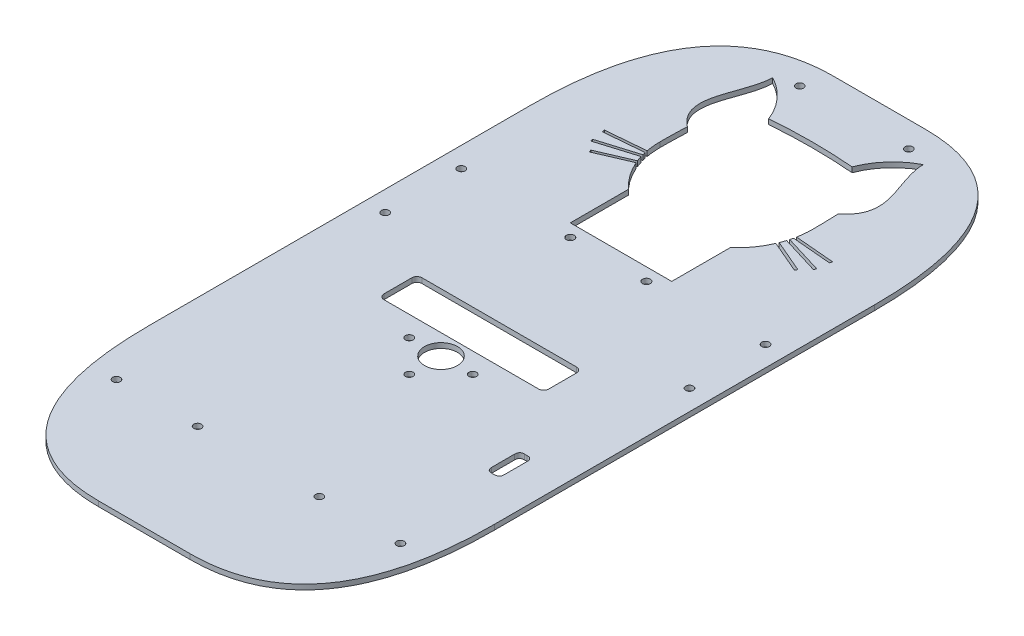
SolidWorks part; units mm, degrees
ref_plane "Спереди" through (0, 0, 0) normal (0, 0, 1) x (1, 0, 0)
ref_plane "Сверху" through (0, 0, 0) normal (0, 1, 0) x (1, 0, 0)
ref_plane "Справа" through (0, 0, 0) normal (1, 0, 0) x (0, 0, -1)
sketch "Эскиз1" plane through (0, 0, 0) normal (0, 1, 0) x (1, 0, 0)
  line L0 (0, 160) -> (0, -130) construction
  line L1 (-68, 160) -> (68, 160)
  line L2 (-68, 160) -> (-68, -130)
  line L3 (-68, -130) -> (68, -130)
  line L4 (68, 160) -> (68, -130)
  line L5 (-68, 0) -> (68, 0) construction
  dimension "D1" = 136
  dimension "D2" = 160
  dimension "D3" = 130
extrude "тело" add sketch "Эскиз1" along normal blind 2
sketch "Эскиз12" plane through (0, 2, 0) normal (0, 1, 0) x (1, 0, 0)
  line L0 (0, 160) -> (0, -130) construction
  line L1 (68, 160) -> (-68, 160) construction
  line L2 (-68, -130) -> (68, -130) construction
  line L3 (60, 55) -> (60, 25) construction
  line L4 (60, 40) -> (-60, 40) construction
  line L5 (-60, 55) -> (-60, 25) construction
  circle A0 centre (60, 55) radius 1.5
  circle A1 centre (-60, 55) radius 1.5
  circle A2 centre (-60, 25) radius 1.5
  circle A3 centre (60, 25) radius 1.5
  point P12 (-60, 40)
  point P17 (0, 40)
  dimension "D2" = 3
  dimension "D1" = 30
  dimension "D3" = 60
  dimension "D4" = 40
extrude "крепление подвески" cut sketch "Эскиз12" against normal through all
sketch "Эскиз8" plane through (0, 2, 0) normal (0, 1, 0) x (1, 0, 0)
  line L0 (-20, -130) -> (20, -130) construction
  line L1 (0, -130) -> (0, 160) construction
  line L2 (-68, -130) -> (68, -130) construction
  line L3 (68, 160) -> (-68, 160) construction
  circle A0 centre (-20, -130) radius 1.5
  circle A1 centre (20, -130) radius 1.5
  point P10 (0, -130)
  dimension "D1" = 3
  dimension "D2" = 40
  dimension "D3" = 130
extrude "крепление камеры" [suppressed] cut sketch "Эскиз8" against normal through all and the other way through all
sketch "Эскиз13" plane through (0, 2, 0) normal (0, 1, 0) x (1, 0, 0)
  line L0 (0, 160) -> (0, -130) construction
  line L1 (68, 160) -> (-68, 160) construction
  line L2 (-68, -130) -> (68, -130) construction
  line L3 (-57, 125) -> (57, 125) construction
  line L4 (-68, 15) -> (68, 15) construction
  line L5 (-57, -10) -> (57, -10) construction
  line L6 (-68, 160) -> (-68, -130) construction
  line L7 (-57, -85) -> (57, -85) construction
  line L8 (68, -130) -> (68, 160) construction
  line L9 (-25, 125) -> (-57, 125) construction
  line L10 (25, 125) -> (57, 125) construction
  line L11 (-57, -10) -> (-25, -10) construction
  line L12 (25, -10) -> (57, -10) construction
  line L13 (-57, -85) -> (-25, -85) construction
  line L14 (25, -85) -> (57, -85) construction
  circle A0 centre (-57, 125) radius 1.5
  circle A1 centre (57, 125) radius 1.5
  circle A2 centre (57, -10) radius 1.5
  circle A3 centre (-57, -10) radius 1.5
  circle A4 centre (-57, -85) radius 1.5
  circle A5 centre (57, -85) radius 1.5
  circle A6 centre (-25, 125) radius 1.5
  circle A7 centre (25, 125) radius 1.5
  circle A8 centre (25, -10) radius 1.5
  circle A9 centre (-25, -10) radius 1.5
  circle A10 centre (-25, -85) radius 1.5
  circle A11 centre (25, -85) radius 1.5
  point P18 (0, 125)
  point P19 (0, -10)
  point P20 (0, -85)
  point P27 (0, 15)
  dimension "D1" = 3
  dimension "D2" = 110
  dimension "D3" = 25
  dimension "D4" = 100
  dimension "D5" = 114
  dimension "D6" = 32
  dimension "D7" = 32
  dimension "D8" = 32
  dimension "D9" = 32
  dimension "D10" = 32
  dimension "D11" = 32
extrude "крепления уголков" [suppressed] cut sketch "Эскиз13" against normal through all
sketch "Эскиз9" plane through (0, 2, 0) normal (0, 1, 0) x (1, 0, 0)
  line L0 (0, -50) -> (0, 50) construction
  line L2 (-68, -130) -> (68, -130) construction
  circle A0 centre (0, -13) radius 6.5
  circle A1 centre (0, -13) radius 12.5 construction
  circle A2 centre (0, -0.5) radius 1.5
  circle A3 centre (12.5, -13) radius 1.5
  circle A4 centre (-12.5, -13) radius 1.5
  circle A5 centre (0, -25.5) radius 1.5
  point P4 (0, -17.1656)
  dimension "D2" = 13
  dimension "D3" = 25
  dimension "D4" = 3
  dimension "D1" = 117
extrude "ось вращения качалки" cut sketch "Эскиз9" against normal through all
sketch "Эскиз5" plane through (0, 2, 0) normal (0, 1, 0) x (1, 0, 0)
  line L0 (-50, -65) -> (50, -25) construction
  line L1 (-50, -25) -> (50, -25) construction
  line L2 (-50, -25) -> (-50, -65) construction
  line L3 (-50, -65) -> (50, -65) construction
  line L4 (50, -25) -> (50, -65) construction
  line L5 (-50, -25) -> (50, -65) construction
  line L6 (-68, -130) -> (68, -130) construction
  circle A0 centre (-50, -25) radius 1.5
  circle A1 centre (50, -25) radius 1.5
  circle A2 centre (50, -65) radius 1.5
  circle A3 centre (-50, -65) radius 1.5
  point P12 (0, -45)
  dimension "D1" = 3
  dimension "D2" = 100
  dimension "D3" = 40
  dimension "D4" = 65
extrude "крепление raspberry" [suppressed] cut sketch "Эскиз5" against normal through all
sketch "Эскиз11" plane through (0, 2, 0) normal (0, 1, 0) x (1, 0, 0)
  line L0 (-32.5, 2.5) -> (32.5, 2.5) construction
  line L1 (-32.5, 10) -> (32.5, 10)
  line L2 (-32.5, 10) -> (-32.5, -5)
  line L3 (-32.5, -5) -> (32.5, -5)
  line L4 (32.5, 10) -> (32.5, -5)
  point P11 (0, 10)
  dimension "D1" = 65
  dimension "D2" = 15
extrude "отверстие под провода на нижний этаж" cut sketch "Эскиз11" against normal through all
fillet "Скругление3" radius 2 4 edges at (-32.5, 1, 5) (32.5, 1, 5) (32.5, 1, -10) (-32.5, 1, -10)
sketch "Эскиз14" [suppressed] plane through (0, 2, 0) normal (0, 1, 0) x (1, 0, 0)
  line L0 (0, 160) -> (0, -130) construction
  line L1 (68, 160) -> (-68, 160) construction
  line L2 (-68, -130) -> (68, -130) construction
  line L3 (-47.5, -125) -> (47.5, -125) construction
  line L4 (47.5, -115) -> (47.5, -135) construction
  line L5 (-12.5, -95) -> (12.5, -95) construction
  line L6 (-47.5, -115) -> (-47.5, -135) construction
  circle A0 centre (-47.5, -115) radius 1.5
  circle A1 centre (-47.5, -135) radius 1.5
  circle A2 centre (47.5, -115) radius 1.5
  circle A3 centre (47.5, -135) radius 1.5
  point P8 (0, -125)
  point P14 (-47.5, -125)
  point P15 (47.5, -125)
  dimension "D1" = 3
  dimension "D2" = 20
  dimension "D3" = 30
  dimension "D4" = 95
extrude "крепление стопоров" [suppressed] cut sketch "Эскиз14" against normal through all
sketch "Эскиз15" plane through (0, 2, 0) normal (0, 1, 0) x (1, 0, 0)
  line L0 (-21.5, 150) -> (21.5, 150) construction
  line L1 (68, 160) -> (-68, 160) construction
  circle A0 centre (21.5, 150) radius 1.5
  circle A1 centre (-21.5, 150) radius 1.5
  point P6 (0, 150)
  dimension "D1" = 3
  dimension "D2" = 10
  dimension "D3" = 43
extrude "Крепление фронтальной камеры" cut sketch "Эскиз15" against normal up to next
sketch "Эскиз16" plane through (0, 2, 0) normal (0, 1, 0) x (1, 0, 0)
  line L0 (-56, -85) -> (-24, -85) construction
  line L1 (-68, -130) -> (68, -130) construction
  line L2 (-68, 160) -> (-68, -130) construction
  line L3 (0, -130) -> (0, 160) construction
  line L4 (68, 160) -> (-68, 160) construction
  circle A0 centre (-56, -85) radius 1.5
  circle A1 centre (-24, -85) radius 1.5
  circle A2 centre (24, -85) radius 1.5
  circle A3 centre (56, -85) radius 1.5
  dimension "D1" = 32
  dimension "D4" = 3
  dimension "D2" = 45
  dimension "D3" = 12
extrude "Крепление силовых уголков со стороны буллета" cut sketch "Эскиз16" against normal up to next
sketch "Эскиз17" plane through (0, 2, 0) normal (0, 1, 0) x (1, 0, 0)
  line L1 (48, -30) -> (53, -30)
  line L2 (48, -30) -> (48, -43)
  line L3 (48, -43) -> (53, -43)
  line L4 (53, -30) -> (53, -43)
  dimension "D2" = 13
  dimension "D3" = 5
extrude "Отверстие по дпитание сервоприводов и шилда" cut sketch "Эскиз17" against normal up to next
sketch "Эскиз18" plane through (0, 2, 0) normal (0, 1, 0) x (1, 0, 0)
  line L0 (0, 0) -> (0, 160) construction
  line L1 (68, 160) -> (-68, 160) construction
  line L2 (-20, 58) -> (20, 58)
  line L3 (20, 58) -> (20, 81)
  line L5 (-20, 81) -> (-20, 58)
  line L6 (10, 58) -> (10, 43)
  line L7 (10, 43) -> (-10, 43)
  line L8 (-10, 43) -> (-10, 58)
  line L9 (28.2843, 93.3607) -> (-28.2843, 93.3607)
  line L11 (-29.2696, 96.7813) -> (-44.8695, 95.4286)
  line L12 (15, 53) -> (-15, 53) construction
  line L13 (-28.6963, 94.613) -> (-43.9353, 89.9676)
  line L16 (-27.5654, 91.5223) -> (-40.4203, 86.0016)
  line L17 (-29.474, 97.7673) -> (-44.9559, 96.4249)
  line L18 (-28.972, 95.5744) -> (-44.2269, 90.9242)
  line L19 (-27.9447, 92.4477) -> (-40.8149, 86.9204)
  line L20 (-44.9559, 96.4249) -> (-44.8695, 95.4286)
  line L21 (-44.2269, 90.9242) -> (-43.9353, 89.9676)
  line L22 (-40.8149, 86.9204) -> (-40.4203, 86.0016)
  line L23 (-29.356, 97.7776) -> (-44.9559, 96.4249) construction
  line L24 (-28.6804, 94.6179) -> (-43.9353, 89.9676) construction
  line L25 (-27.5501, 91.5289) -> (-40.4203, 86.0016) construction
  line L26 (40.8149, 86.9204) -> (40.4203, 86.0016)
  line L27 (44.2269, 90.9242) -> (43.9353, 89.9676)
  line L28 (44.9559, 96.4249) -> (44.8695, 95.4286)
  line L29 (27.9447, 92.4477) -> (40.8149, 86.9204)
  line L30 (28.972, 95.5744) -> (44.2269, 90.9242)
  line L31 (29.474, 97.7673) -> (44.9559, 96.4249)
  line L32 (27.5654, 91.5223) -> (40.4203, 86.0016)
  line L33 (28.6963, 94.613) -> (43.9353, 89.9676)
  line L34 (29.2696, 96.7813) -> (44.8695, 95.4286)
  arc A0 (20, 81) -> (-20, 81) centre (0, 103.3607) ccw construction
  circle A1 centre (15, 53) radius 1.55
  circle A2 centre (-15, 53) radius 1.55
  arc A4 (-30, 103.3607) -> (-28.2843, 131.3607) centre (199.3322, 103.3607) cw
  arc A5 (-28.2843, 131.3607) -> (28.2843, 131.3607) centre (0, -67.6393) cw
  arc A6 (28.2843, 131.3607) -> (30, 103.3607) centre (-199.3322, 103.3607) cw
  arc A7 (-20, 81) -> (-27.5654, 91.5223) centre (0, 103.3607) cw
  arc A8 (20, 81) -> (27.5654, 91.5223) centre (0, 103.3607) ccw
  arc A9 (29.474, 97.7673) -> (30, 103.3607) centre (0, 103.3607) ccw
  arc A10 (-29.7135, 147.5209) -> (-16.4423, 132.687) centre (-42.569, 122.6661) cw
  arc A11 (29.7135, 147.5209) -> (16.4423, 132.687) centre (42.569, 122.6661) ccw
  arc A12 (28.972, 95.5744) -> (29.2696, 96.7813) centre (0, 103.3607) ccw
  arc A13 (27.9447, 92.4477) -> (28.6963, 94.613) centre (0, 103.3607) ccw
  arc A14 (-27.9447, 92.4477) -> (-28.6963, 94.613) centre (0, 103.3607) cw
  arc A15 (-28.972, 95.5744) -> (-29.2696, 96.7813) centre (0, 103.3607) cw
  arc A16 (-29.474, 97.7673) -> (-30, 103.3607) centre (0, 103.3607) cw
  spline S0 degree 3 poles (-29.7571, 113.9123) (-42.1018, 123.5014) (-29.7562, 136.265) (-29.7135, 147.5209) knots 0 0 0 0 1 1 1 1
  spline S1 degree 3 poles (29.7571, 113.9123) (42.1018, 123.5014) (29.7562, 136.265) (29.7135, 147.5209) knots 0 0 0 0 1 1 1 1
  point P9 (0, 43)
  point P15 (0, 58)
  point P25 (0, 53)
  dimension "D6" = 60
  dimension "D8" = 3.1
  dimension "D1" = 40
  dimension "D2" = 20
  dimension "D3" = 15
  dimension "D4" = 23
  dimension "D5" = 10
  dimension "D9" = 5
  dimension "D10" = 30
  dimension "D11" = 38
  dimension "D12" = 56.5685
  dimension "D13" = 1
  dimension "D14" = 1
  dimension "D15" = 1
fillet "Скругление4" radius 50 2 edges at (68, 1, 130) (-68, 1, -160) second distance 70 conic rho 0.5 first distance on face at (0, 1, 130) first distance on face at (0, 1, -160)
fillet "Скругление5" radius 70 2 edges at (-68, 1, 130) (68, 1, -160) second distance 50 conic rho 0.5 first distance on face at (-68, 1.25, -35) first distance on face at (68, 1.25, 5)
fillet "Скругление6" radius 2 4 edges at (48, 1, 43) (53, 1, 43) (48, 1, 30) (53, 1, 30) conic rho 0.5
sketch "Эскиз19" plane through (0, 2, 0) normal (0, 1, 0) x (1, 0, 0)
  line L1 (-95.3857, 162.9355) -> (76.7354, 162.9355)
  line L2 (-95.3857, 162.9355) -> (-95.3857, 60)
  line L3 (-95.3857, 60) -> (76.7354, 60)
  line L4 (76.7354, 162.9355) -> (76.7354, 60)
  circle A0 centre (-60, 55) radius 1.5 construction
  dimension "D1" = 5
extrude "Вырез-Вытянуть3" [suppressed] cut sketch "Эскиз19" against normal up to next
fillet "Скругление8" [suppressed] radius 10
extrude "Вырез под манипулятор" cut sketch "Эскиз18" against normal up to next contours S0 A4 A5 A10 | A6 S1 A11 A5 | A16 L17 L20 L11 A15 L18 L21 L13 A14 L9 A13 L33 L27 L30 A12 L34 L28 L31 A9 A6 A5 A4 | A14 L19 L22 L16 A7 L5 L2 L3 A8 L32 L26 L29 A13 L9 | A1 | A2 region at (0, 2, -76.9456) region at (0, 2, -112.4371) region at (-27.968, 2, -132.7806) region at (27.968, 2, -132.7806) region at (15, 2, -53) region at (-15, 2, -53)
